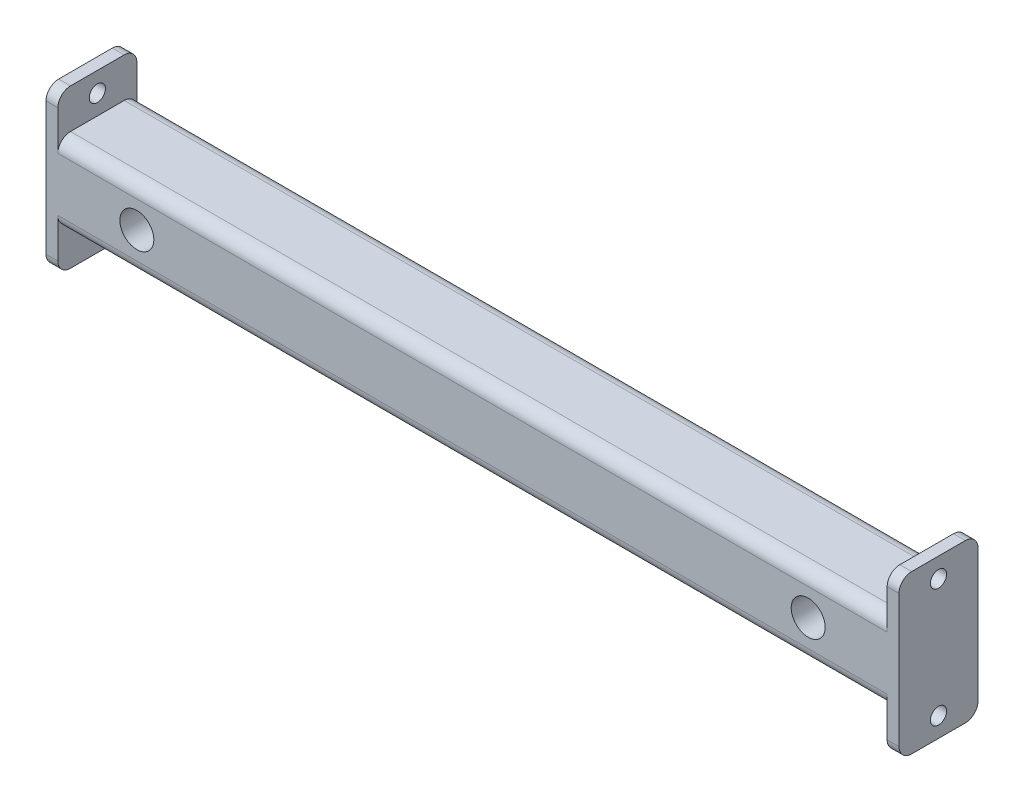
SolidWorks part; units mm, degrees
ref_plane "Płaszczyzna przednia" through (0, 0, 0) normal (0, 0, 1) x (1, 0, 0)
ref_plane "Płaszczyzna górna" through (0, 0, 0) normal (0, 1, 0) x (1, 0, 0)
ref_plane "Płaszczyzna prawa" through (0, 0, 0) normal (1, 0, 0) x (0, 0, -1)
sketch "Szkic3" plane through (0, 0, 0) normal (1, 0, 0) x (0, 0, -1)
  line L0 (-9.6, 16) -> (9.6, 16)
  line L1 (-13.6, -20) -> (13.6, -20)
  line L2 (-20, -13.6) -> (-20, 13.6)
  line L3 (-13.6, 20) -> (13.6, 20)
  line L4 (20, -13.6) -> (20, 13.6)
  line L5 (-20, -20) -> (20, 20) construction
  line L6 (-20, 20) -> (20, -20) construction
  line L7 (16, -9.6) -> (16, 9.6)
  line L8 (-9.6, -16) -> (9.6, -16)
  line L9 (-16, -9.6) -> (-16, 9.6)
  line L10 (-16, -16) -> (16, -16) construction
  line L11 (-16, -16) -> (-16, 16) construction
  line L12 (16, -16) -> (16, 16) construction
  line L13 (-16, 16) -> (16, 16) construction
  line L14 (-20, -20) -> (20, -20) construction
  line L15 (20, -20) -> (20, 20) construction
  line L16 (-20, -20) -> (-20, 20) construction
  line L17 (-20, 20) -> (20, 20) construction
  arc A0 (-9.6, -16) -> (-16, -9.6) centre (-9.6, -9.6) cw
  arc A1 (16, -9.6) -> (9.6, -16) centre (9.6, -9.6) cw
  arc A2 (9.6, 16) -> (16, 9.6) centre (9.6, 9.6) cw
  arc A3 (-9.6, 16) -> (-16, 9.6) centre (-9.6, 9.6) ccw
  arc A4 (13.6, -20) -> (20, -13.6) centre (13.6, -13.6) ccw
  arc A5 (-13.6, -20) -> (-20, -13.6) centre (-13.6, -13.6) cw
  arc A6 (-20, 13.6) -> (-13.6, 20) centre (-13.6, 13.6) cw
  arc A7 (13.6, 20) -> (20, 13.6) centre (13.6, 13.6) cw
  point P0 (0, 0)
  dimension "D4" = 6.4
  dimension "D1" = 40
  dimension "D2" = 40
  dimension "D3" = 4
extrude "Dodanie-wyciągnięcie2" add sketch "Szkic3" along normal blind 420
sketch "Szkic4" plane through (420, 0, 0) normal (1, 0, 0) x (0, 0, -1)
  line L0 (55, 0) -> (-55, 0) construction
  line L1 (-13.6, -40) -> (13.6, -40)
  line L2 (-20, -33.6) -> (-20, 33.6)
  line L3 (-13.6, 40) -> (13.6, 40)
  line L4 (20, -33.6) -> (20, 33.6)
  line L5 (-20, -40) -> (20, 40) construction
  line L6 (-20, 40) -> (20, -40) construction
  line L7 (0, 55) -> (0, -55) construction
  circle A0 centre (0, 30) radius 4.1
  circle A1 centre (0, -30) radius 4.1
  arc A2 (13.6, -40) -> (20, -33.6) centre (13.6, -33.6) ccw
  arc A3 (13.6, 40) -> (20, 33.6) centre (13.6, 33.6) cw
  arc A4 (-20, 33.6) -> (-13.6, 40) centre (-13.6, 33.6) cw
  arc A5 (-13.6, -40) -> (-20, -33.6) centre (-13.6, -33.6) cw
  point P0 (0, 0)
  dimension "D3" = 8.2
  dimension "D5" = 6.4
  dimension "D1" = 40
  dimension "D2" = 80
  dimension "D4" = 30
extrude "Dodanie-wyciągnięcie3" add sketch "Szkic4" along normal blind 6
ref_plane "Płaszczyzna1" through (210, 0, 0) normal (1, 0, 0) x (0, 0, -1)
sketch "Szkic5" plane through (0, 0, 20) normal (0, 0, 1) x (1, 0, 0)
  line L0 (55, 0) -> (-55, 0) construction
  line L1 (0, -55) -> (0, 55) construction
  circle A0 centre (25, 0) radius 8.6
  circle A1 centre (25, 0) radius 15
  dimension "D1" = 17.2
  dimension "D2" = 30
  dimension "D5" = 25
mirror "Lustro4" about plane through (210, 0, 0) normal (1, 0, 0) of "Dodanie-wyciągnięcie3"
sketch "Szkic6" plane through (0, 0, -20) normal (0, 0, -1) x (-1, 0, 0)
  line L0 (-210, 22) -> (-210, -22) construction
  circle A0 centre (-40, 0) radius 13.5
  circle A1 centre (-40, 0) radius 8.6
  circle A2 centre (-40, 0) radius 8.6
  dimension "D1" = 17.2
  dimension "D2" = 27
  dimension "D3" = 170
extrude "Wytnij-wyciągnięcie1" cut sketch "Szkic6" against normal through all contours A1
extrude "Dodanie-wyciągnięcie5" add sketch "Szkic6<3>" against normal through all contours A0 | A1
sketch "Szkic6<3>" plane through (0, 0, -20) normal (0, 0, -1) x (-1, 0, 0) same geometry as "Szkic6"
mirror "Lustro6" about plane through (210, 0, 0) normal (1, 0, 0) of "Wytnij-wyciągnięcie1", "Dodanie-wyciągnięcie5"
